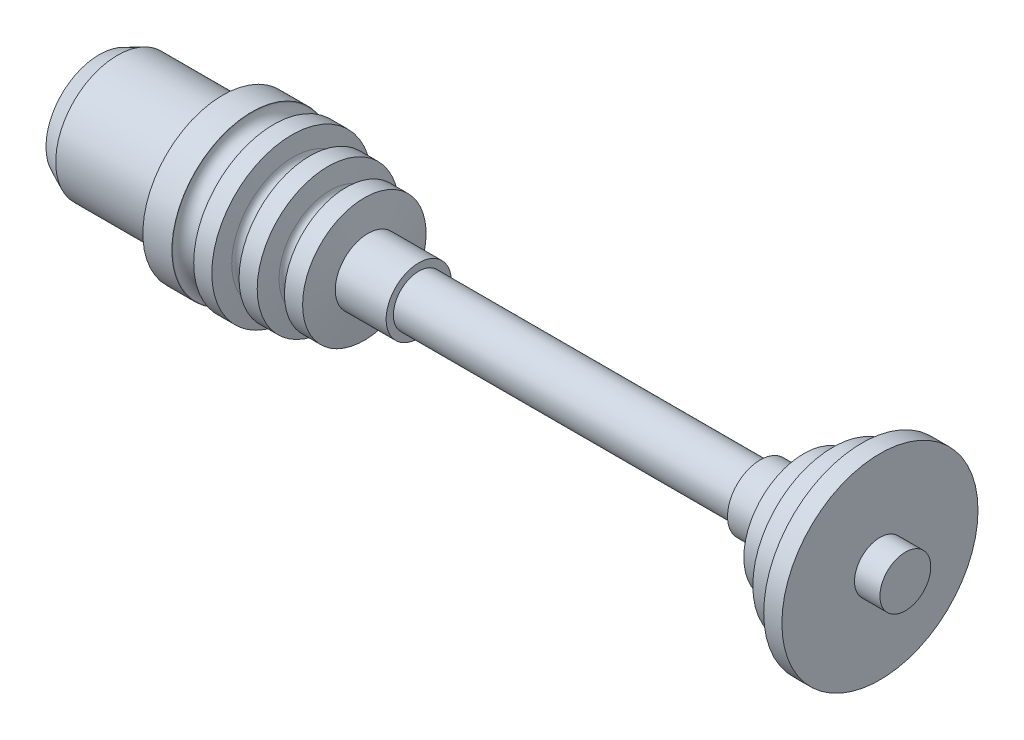
SolidWorks part; units mm, degrees
ref_plane "Front Plane" through (0, 0, 0) normal (0, 0, 1) x (1, 0, 0)
ref_plane "Top Plane" through (0, 0, 0) normal (0, 1, 0) x (1, 0, 0)
ref_plane "Right Plane" through (0, 0, 0) normal (1, 0, 0) x (0, 0, -1)
sketch "Sketch1" plane through (0, 0, 0) normal (1, 0, 0) x (0, 0, -1)
  circle A0 centre (0, 0) radius 1.7
  dimension "D1" = 3.4
extrude "Boss-Extrude1" add sketch "Sketch1" along normal blind 2.9
sketch "Sketch2" plane through (2.9, 0, 0) normal (1, 0, 0) x (0, 0, -1)
  circle A0 centre (0, 0) radius 2.2
  dimension "D1" = 4.4
extrude "Boss-Extrude2" add sketch "Sketch2" along normal blind 0.8
sketch3d "3DSketch1"
  line L0 (-29.1313, 0, 0) -> (29.1313, 0, 0) construction
sketch "Sketch3" plane through (0, 0, 0) normal (0, 0, 1) x (1, 0, 0)
  line L0 (4.3, 2.2) -> (4.7984, 2.2)
  line L1 (-29.1313, 0) -> (29.1313, 0) construction
  line L2 (5.2984, 1.95) -> (5.7984, 1.95)
  line L3 (6.2984, 1.7) -> (6.7984, 1.7)
  line L4 (4.7984, 2.2) -> (4.8467, 1.7)
  line L5 (5.2984, 1.95) -> (5.2562, 1.7)
  line L6 (5.7984, 1.95) -> (5.8591, 1.4096)
  line L7 (6.2984, 1.7) -> (6.2342, 1.4096)
  line L8 (6.7984, 1.7) -> (6.8978, 0.9)
  line L9 (6.8978, 0.9) -> (8.2978, 0.9)
  line L10 (8.2978, 0.9) -> (8.2978, 0)
  line L11 (8.2978, 0) -> (3.6999, 0)
  line L12 (3.6999, 0) -> (3.7, 2.2)
  arc A0 (3.7, 2.2) -> (4.3, 2.2) centre (4, 2.1922) ccw
  arc A1 (4.8467, 1.7) -> (5.2562, 1.7) centre (5.0514, 1.7198) ccw
  arc A2 (5.8591, 1.4096) -> (6.2342, 1.4096) centre (6.0466, 1.4306) ccw
  dimension "D12" = 0.3001
  dimension "D1" = 0.6
  dimension "D2" = 2.2
  dimension "D3" = 1.95
  dimension "D4" = 0.5
  dimension "D5" = 0.5
  dimension "D6" = 1.7
  dimension "D7" = 0.5
  dimension "D8" = 0.5
  dimension "D9" = 0.9
  dimension "D10" = 1.4
  dimension "D15" = 97.084
  dimension "D16" = 0.9
revolve "Revolve2" add sketch "Sketch3" angle 360 about L0 region at (5.6372, 0.8335, 0)
sketch "Sketch4" plane through (8.2978, 0, 0) normal (1, 0, 0) x (0, 0, -1)
  circle A0 centre (0, 0) radius 0.7
  dimension "D1" = 1.4
extrude "Boss-Extrude3" add sketch "Sketch4" along normal blind 9.4
sketch "Sketch5" plane through (17.6978, 0, 0) normal (1, 0, 0) x (0, 0, -1)
  circle A0 centre (0, 0) radius 0.9
  dimension "D1" = 1.8
extrude "Boss-Extrude4" add sketch "Sketch5" along normal blind 1.2
sketch "Sketch7" plane through (0, 0, 0) normal (0, 0, 1) x (1, 0, 0)
  line L0 (18.8978, 1.65) -> (19.3978, 1.65)
  line L1 (-29.1313, 0) -> (29.1313, 0) construction
  line L3 (19.6949, 2.2) -> (20.1949, 2.2)
  line L4 (20.4949, 2.7) -> (20.9949, 2.7)
  line L5 (18.8978, 1.65) -> (18.8978, 0)
  line L6 (18.8978, -0.9) -> (18.8978, 0.9) construction
  line L7 (20.1949, 2.2) -> (20.2928, 0.8583)
  line L8 (19.3978, 1.65) -> (19.4801, 1.0128)
  line L9 (19.6949, 2.2) -> (19.6104, 0.9982)
  line L10 (20.4949, 2.7) -> (20.4454, 0.8355)
  line L11 (20.9949, 2.7) -> (20.9949, 0.7)
  line L12 (20.9949, 0.7) -> (21.6949, 0.7)
  line L13 (21.6949, 0.7) -> (21.6949, 0)
  line L14 (21.6949, 0) -> (18.8978, 0)
  arc A0 (19.4801, 1.0128) -> (19.6104, 0.9982) centre (19.547, 1.0214) ccw
  arc A1 (20.2928, 0.8583) -> (20.4454, 0.8355) centre (20.3717, 0.8641) ccw
  dimension "D1" = 0.5
  dimension "D2" = 1.65
  dimension "D3" = 0.297
  dimension "D4" = 0.3
  dimension "D5" = 0.5
  dimension "D6" = 0.5
  dimension "D7" = 0.7
  dimension "D8" = 0.7
  dimension "D9" = 2.7
  dimension "D10" = 2.2
revolve "Revolve3" add sketch "Sketch7" angle 360 about L0
sketch3d "3DSketch2"
  circle A0 centre (0, 0, 0) radius 1.7 construction
  circle A1 centre (0, 0, 0) radius 1.7
  point P2 (1.7, 0, 0)
  point P4 (1.7, 0, 0)
extrude "Boss-Extrude5" add sketch "3DSketch2" along direction (1, 0, 0) on the side against the normal blind 0.5 draft 25 contours A1
